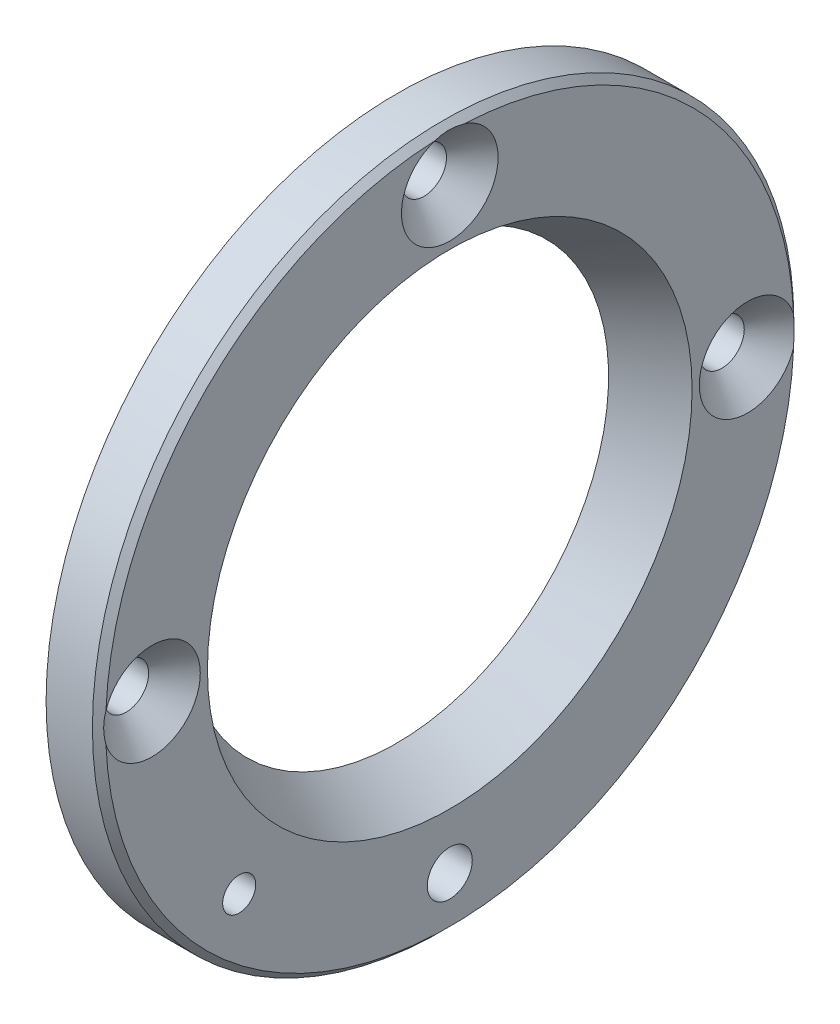
SolidWorks part; units mm, degrees
ref_plane "Face" through (0, 0, 0) normal (0, 0, 1) x (1, 0, 0)
ref_plane "Dessus" through (0, 0, 0) normal (0, 1, 0) x (1, 0, 0)
ref_plane "Droite" through (0, 0, 0) normal (1, 0, 0) x (0, 0, -1)
sketch "Esquisse1" plane through (0, 0, 0) normal (0, 0, 1) x (1, 0, 0)
  line L0 (0, 0) -> (20, 0) construction
  line L1 (0, 16) -> (0, 26.5)
  line L2 (0, 26.5) -> (4, 26.5)
  line L3 (4, 26.5) -> (4, 16)
  line L4 (4, 16) -> (0, 16)
  dimension "D1" = 32
  dimension "D2" = 53
  dimension "D3" = 4
revolve "Révolution1" add sketch "Esquisse1" angle 360 about L0
chamfer "Chanfrein1" distance 4 angle 30 1 edges at (4, 0, 16) first distance on face at (4, 0, 16)
sketch "Esquisse2" plane through (4, 0, 0) normal (1, 0, 0) x (0, 0, -1)
  line L0 (-22.5, 0) -> (22.5, 0) construction
  line L1 (0, 22.5) -> (0, -22.5) construction
  line L2 (0, 0) -> (-15.9099, -15.9099) construction
  circle A0 centre (0, 0) radius 22.5 construction
  dimension "D1" = 45
  dimension "D2" = 45
sketch "Esquisse7" plane through (4, 0, 0) normal (1, 0, 0) x (0, 0, -1)
  circle A0 centre (0, -22.5) radius 1.7
extrude "Enlèv. mat.-Extru.2" cut sketch "Esquisse7" against normal up to next
hole_wizard "Fraisage pour vis à tête fraisée M31" positions "Esquisse4" profile "Esquisse3" countersink size "M3" standard "Din" end condition through all
sketch "Esquisse4" plane through (4, 0, 0) normal (1, 0, 0) x (0, 0, -1)
  point P0 (0, 22.5)
  point P12 (-22.5, 0)
  point P15 (22.5, 0)
sketch "Esquisse3" plane through (4, 22.5, 0) normal (0, 1, 0) x (0, 0, -1)
  line L0 (0, 0) -> (0, 4)
  line L1 (0, 4) -> (1.7, 4)
  line L2 (1.7, 4) -> (1.7, 1.95)
  line L3 (1.7, 1.95) -> (3.65, 0)
  line L5 (3.65, 0) -> (0, 0)
  line L6 (-1.7, 1.95) -> (-3.65, 0) construction
  line L11 (0, -6.35) -> (0, 107.95) construction
  dimension "Diamètre du perçage jusqu'au prochain" = 3.4
  dimension "Profondeur du perçage jusqu'au prochain" = 4
  dimension "Diamètre du fraisage entrant" = 7.3
  dimension "Angle du fraisage entrant" = 90
hole_wizard "Trou taraudé M31" positions "Esquisse6" profile "Esquisse5" tap size "M3" standard "Iso" end condition up to next
sketch "Esquisse6" plane through (4, 0, 0) normal (1, 0, 0) x (0, 0, -1)
  point P0 (-15.9099, -15.9099)
sketch "Esquisse5" plane through (4, -15.9099, 15.9099) normal (0, 1, 0) x (0, 0, -1)
  line L0 (0, 0) -> (0, 4)
  line L1 (0, 4) -> (1.25, 4)
  line L2 (1.25, 4) -> (1.25, 0)
  line L5 (1.25, 0) -> (0, 0)
  line L11 (0, -6.35) -> (0, 107.95) construction
  dimension "Diamètre du trou pour taraudage jusqu'au prochain" = 2.5
  dimension "Profondeur du trou pour taraudage jusqu'au prochain" = 4
cosmetic thread "Filetage de perçage1" parameters "D2"=3
chamfer "Chanfrein2" distance 0.5 angle 45 1 edges at (4, 0, 26.5)
